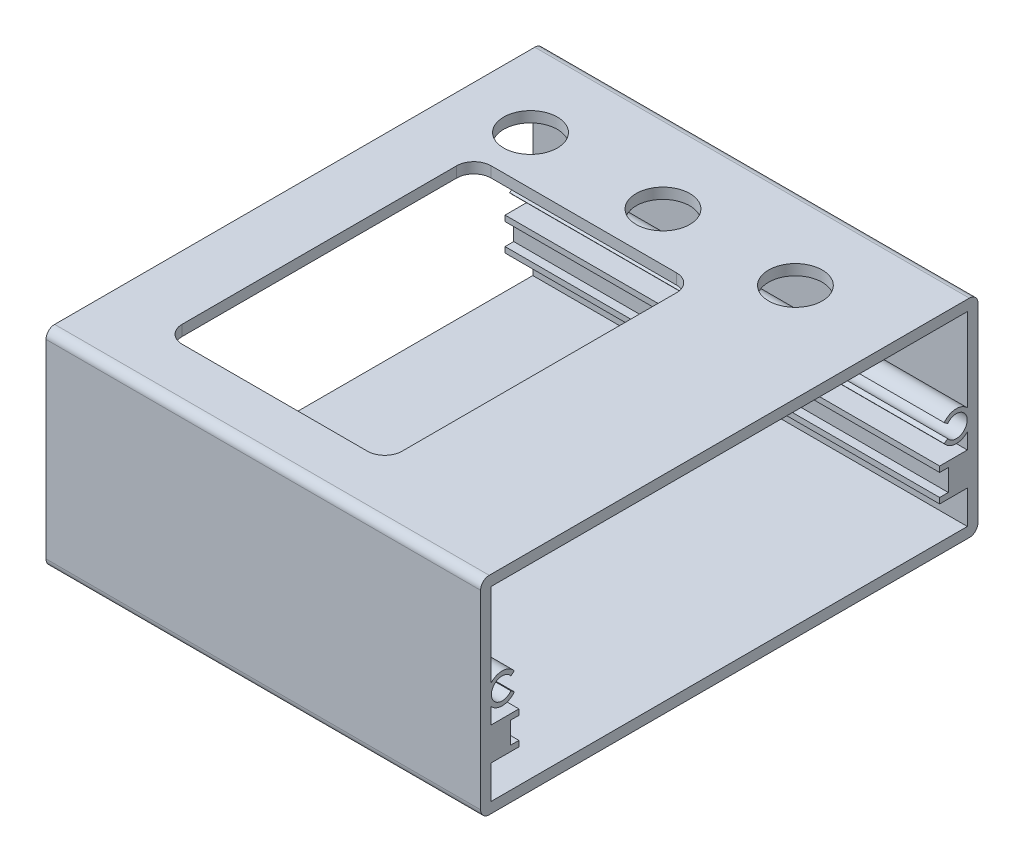
SolidWorks part; units mm, degrees
ref_plane "Front Plane" through (0, 0, 0) normal (0, 0, 1) x (1, 0, 0)
ref_plane "Top Plane" through (0, 0, 0) normal (0, 1, 0) x (1, 0, 0)
ref_plane "Right Plane" through (0, 0, 0) normal (1, 0, 0) x (0, 0, -1)
sketch "Sketch1" plane through (0, 0, 0) normal (1, 0, 0) x (0, 0, -1)
  line L0 (-28.73, 11.98) -> (28.73, 11.98)
  line L1 (-27.5, 10.75) -> (27.5, 10.75)
  line L2 (-27.5, 10.75) -> (-27.5, -10.75)
  line L3 (-27.5, -10.75) -> (27.5, -10.75)
  line L4 (27.5, 10.75) -> (27.5, -10.75)
  line L5 (-27.5, 10.75) -> (27.5, -10.75) construction
  line L6 (-27.5, -10.75) -> (27.5, 10.75) construction
  line L7 (28.73, 11.98) -> (28.73, -11.98)
  line L8 (-28.73, -11.98) -> (28.73, -11.98)
  line L9 (-28.73, 11.98) -> (-28.73, -11.98)
  line L10 (0, 10.75) -> (0, -10.75) construction
  line L11 (-24.3, -5) -> (-27.5, -5) construction
  line L12 (-27.5, -6.9) -> (-24.3, -6.9)
  line L13 (-27.5, -6.9) -> (-27.5, -3.1)
  line L14 (-27.5, -3.1) -> (-24.3, -3.1)
  line L15 (-24.3, -6.9) -> (-24.3, -3.1)
  line L16 (-25.3, -5) -> (-24.3, -5) construction
  line L17 (-24.3, -3.75) -> (-25.3, -3.75)
  line L18 (-24.3, -3.75) -> (-24.3, -6.25)
  line L19 (-24.3, -6.25) -> (-25.3, -6.25)
  line L20 (-25.3, -3.75) -> (-25.3, -6.25)
  line L21 (-25.23, 0.67) -> (-25.23, -0.83)
  line L22 (-25.23, 0.67) -> (-24.83, 0.97)
  line L23 (-25.23, -0.83) -> (-24.83, -1.13)
  line L24 (25.23, 0.67) -> (25.23, -0.83)
  line L25 (27.5, -6.9) -> (24.3, -6.9)
  line L26 (24.3, -6.25) -> (25.3, -6.25)
  line L27 (25.3, -3.75) -> (25.3, -6.25)
  line L28 (24.3, -3.75) -> (25.3, -3.75)
  line L29 (24.3, -6.9) -> (24.3, -3.1)
  line L30 (27.5, -3.1) -> (24.3, -3.1)
  line L31 (25.23, -0.83) -> (24.83, -1.13)
  line L32 (25.23, 0.67) -> (24.83, 0.97)
  circle A0 centre (-26.23, -0.08) radius 1.75
  circle A1 centre (-26.23, -0.08) radius 1.25
  circle A2 centre (26.23, -0.08) radius 1.25
  circle A3 centre (26.23, -0.08) radius 1.75
  point P0 (0, 0)
  dimension "D9" = 3.5
  dimension "D1" = 55
  dimension "D2" = 21.5
  dimension "D4" = 3.85
  dimension "D5" = 3.8
  dimension "D6" = 3.2
  dimension "D7" = 2.5
  dimension "D8" = 1
  dimension "D10" = 2.5
  dimension "D11" = 11.9
  dimension "D12" = 1
  dimension "D3" = 1.23
  dimension "D13" = 0.5
extrude "Boss-Extrude1" add sketch "Sketch1" along normal blind 50.2 contours L0 L9 L8 L7 L4 A3 L3 L2 A0 L1 | A1 L22 A0 L2 L23 | L2 A0 | L20 L17 L15 L14 L2 L12 L19 | A3 L4 | A3 L4 L32 A2 L31 | L4 L30 L29 L28 L27 L26 L25 region at (0, 11.3574, 0) region at (0, 1.6231, 26.1318) region at (0, -0.08, 27.6945) region at (0, -0.08, -27.6945) region at (0, -0.08, -27.4956) region at (0, -5, 26.1847) region at (0, -5, -26.1847)
fillet "Fillet1" radius 1 4 edges at (25.1, -11.98, -28.73) (25.1, 11.98, -28.73) (25.1, -11.98, 28.73) (25.1, 11.98, 28.73)
sketch "Sketch2" plane through (0, 11.98, 0) normal (0, 1, 0) x (1, 0, 0)
  circle A0 centre (38.8895, 18.95) radius 3 construction
  circle A1 centre (23.5895, 18.95) radius 3 construction
  circle A2 centre (8.2895, 18.95) radius 3 construction
  circle A3 centre (8.2895, 18.95) radius 3
  circle A4 centre (23.5895, 18.95) radius 3
  circle A5 centre (38.8895, 18.95) radius 3
  circle A6 centre (8.2895, 18.95) radius 3.1
  circle A7 centre (23.5895, 18.95) radius 3.1
  circle A8 centre (38.8895, 18.95) radius 3.1
  dimension "D1" = 0.1
extrude "Cut-Extrude1" cut sketch "Sketch2" against normal up to next contours A6 A3 | A3 | A7 A4 | A4 | A8 A5 | A5 region at (8.2895, 11.98, -18.95) region at (23.5895, 11.98, -18.95) region at (38.8895, 11.98, -18.95) region at (5.2772, 11.98, -18.95) region at (20.5772, 11.98, -18.95) region at (35.8772, 11.98, -18.95)
sketch "Sketch3" plane through (0, 11.98, 0) normal (0, 1, 0) x (1, 0, 0)
  line L0 (9.35, -22.35) -> (30.75, -22.35)
  line L1 (32.75, -20.35) -> (32.75, 11.35)
  line L2 (30.75, 13.35) -> (9.35, 13.35)
  line L3 (7.35, 11.35) -> (7.35, -20.35)
  line L4 (50.2, -27.73) -> (50.2, 27.73)
  line L5 (50.2, 27.73) -> (0, 27.73)
  line L6 (0, 27.73) -> (0, -27.73)
  line L7 (0, -27.73) -> (50.2, -27.73)
  line L8 (50.2, -27.73) -> (50.2, 27.73)
  line L9 (50.2, 27.73) -> (0, 27.73)
  line L10 (0, 27.73) -> (0, -27.73)
  line L11 (0, -27.73) -> (50.2, -27.73)
  line L12 (6.85, 11.35) -> (6.85, -20.35)
  line L13 (30.75, 13.85) -> (9.35, 13.85)
  line L14 (33.25, -20.35) -> (33.25, 11.35)
  line L15 (9.35, -22.85) -> (30.75, -22.85)
  line L16 (6.85, 11.35) -> (6.85, -20.35)
  line L17 (30.75, 13.85) -> (9.35, 13.85)
  line L18 (33.25, -20.35) -> (33.25, 11.35)
  line L19 (9.35, -22.85) -> (30.75, -22.85)
  arc A0 (30.75, -22.35) -> (32.75, -20.35) centre (30.75, -20.35) ccw
  arc A1 (32.75, 11.35) -> (30.75, 13.35) centre (30.75, 11.35) ccw
  arc A2 (9.35, 13.35) -> (7.35, 11.35) centre (9.35, 11.35) ccw
  arc A3 (7.35, -20.35) -> (9.35, -22.35) centre (9.35, -20.35) ccw
  arc A4 (9.35, 13.85) -> (6.85, 11.35) centre (9.35, 11.35) ccw
  arc A5 (33.25, 11.35) -> (30.75, 13.85) centre (30.75, 11.35) ccw
  arc A6 (30.75, -22.85) -> (33.25, -20.35) centre (30.75, -20.35) ccw
  arc A7 (6.85, -20.35) -> (9.35, -22.85) centre (9.35, -20.35) ccw
  arc A8 (9.35, 13.85) -> (6.85, 11.35) centre (9.35, 11.35) ccw
  arc A9 (33.25, 11.35) -> (30.75, 13.85) centre (30.75, 11.35) ccw
  arc A10 (30.75, -22.85) -> (33.25, -20.35) centre (30.75, -20.35) ccw
  arc A11 (6.85, -20.35) -> (9.35, -22.85) centre (9.35, -20.35) ccw
  dimension "D1" = 0
  dimension "D2" = 0
  dimension "D3" = 0.5
extrude "Cut-Extrude2" cut sketch "Sketch3" against normal up to next contours L3 A3 L0 A0 L1 A1 L2 A2 region at (20.05, 11.98, 4.5)
